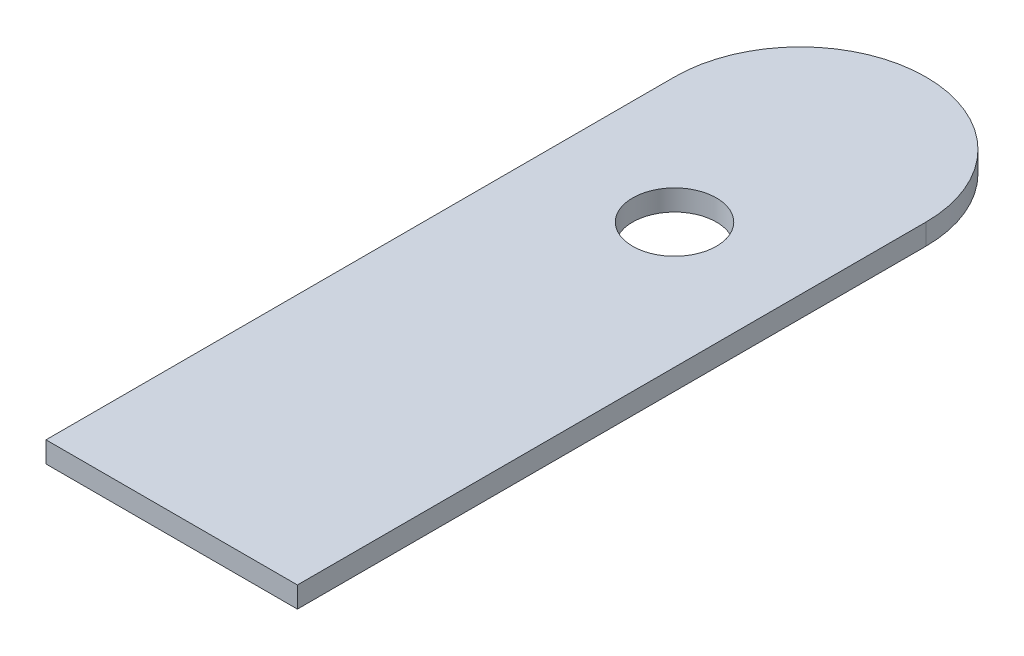
SolidWorks part; units mm, degrees
material "Plain Carbon Steel"
ref_plane "Front Plane" through (0, 0, 0) normal (1, 0, 0) x (0, 1, 0)
ref_plane "Top Plane" through (0, 0, 0) normal (0, 0, 1) x (0, 1, 0)
ref_plane "Right Plane" through (0, 0, 0) normal (0, 1, 0) x (-1, 0, 0)
sketch "Sketch1" plane through (0, 0, 0) normal (0, 1, 0) x (-1, 0, 0)
  line L0 (-38.1, -38.1) -> (38.1, -38.1) construction
  line L1 (38.1, -114.3) -> (-38.1, -114.3)
  line L2 (38.1, -114.3) -> (38.1, 114.3)
  line L3 (38.1, 114.3) -> (-38.1, 114.3)
  line L4 (-38.1, -114.3) -> (-38.1, 114.3)
  line L5 (38.1, -114.3) -> (-38.1, 114.3) construction
  line L6 (38.1, 114.3) -> (-38.1, -114.3) construction
  circle A0 centre (0, -38.1) radius 12.7
  point P0 (0, 0)
  dimension "D4" = 25.4
  dimension "D1" = 228.6
  dimension "D2" = 76.2
  dimension "D3" = 76.2
extrude "Boss-Extrude1" add sketch "Sketch1" along normal blind 6.35
fillet "Fillet1" radius 38.1 2 edges at (-38.1, 3.175, -114.3) (38.1, 3.175, -114.3)
